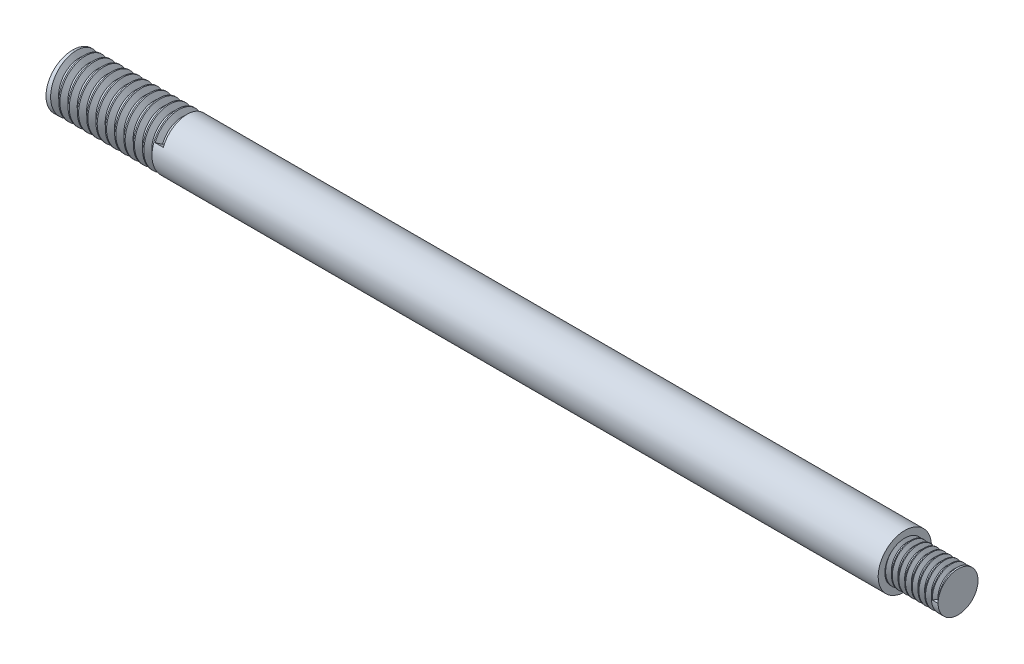
SolidWorks part; units mm, degrees
ref_plane "Front Plane" through (0, 0, 0) normal (0, 0, 1) x (1, 0, 0)
ref_plane "Top Plane" through (0, 0, 0) normal (0, 1, 0) x (1, 0, 0)
ref_plane "Right Plane" through (0, 0, 0) normal (1, 0, 0) x (0, 0, -1)
sketch "Sketch1" plane through (0, 0, 0) normal (0, 0, 1) x (1, 0, 0)
  line L0 (0, 0) -> (0, 2)
  line L1 (0, 2) -> (62.5, 2)
  line L2 (62.5, 2) -> (62.5, 1.5)
  line L3 (62.5, 1.5) -> (66.5, 1.5)
  line L4 (66.5, 1.5) -> (66.5, 0)
  line L5 (66.5, 0) -> (0, 0)
  dimension "D1" = 62.5
  dimension "D2" = 4
  dimension "D3" = 1.5
  dimension "D4" = 2
revolve "Revolve1" add sketch "Sketch1" angle 360 about L5
thread "Thread1" pitch 0.7 method cut profile "Thread Profile1" start angle 0, offset 0, length 8, pitch 0.7, diameter 4
ref_plane "Plane1" through (0, 0, -2) normal (0, -1, 0) x (0, 0, -1)
sketch "Thread Profile1" plane through (0, 0, -2) normal (0, -1, 0) x (0, 0, -1)
  line L0 (0, 0) -> (0, 0.7) construction
  line L11 (0, 0) -> (0, 0.6125)
  line L12 (0, 0.6125) -> (-0.3789, 0.3937)
  line L13 (-0.3789, 0.3937) -> (-0.3789, 0.2187)
  line L15 (-0.3789, 0.2187) -> (0, 0)
  line L17 (-0.3789, 0.3062) -> (0, 0.3062) construction
  point P2 (0, 0)
  dimension "Pitch" = 0.7
  dimension "Profile_Angle" = 60
  dimension "Profile_Land" = 0.175
  dimension "Profile_Height" = 0.3789
thread "Thread2" pitch 0.5 method cut profile "Thread Profile2" start angle 0, offset 0, length 4, pitch 0.5, diameter 3
ref_plane "Plane2" through (66.5, 0, 1.5) normal (0, -1, 0) x (0, 0, 1)
sketch "Thread Profile2" plane through (66.5, 0, 1.5) normal (0, -1, 0) x (0, 0, 1)
  line L0 (0, 0) -> (0, 0.5) construction
  line L11 (0, 0) -> (0, 0.4375)
  line L12 (0, 0.4375) -> (-0.2706, 0.2812)
  line L13 (-0.2706, 0.2812) -> (-0.2706, 0.1562)
  line L15 (-0.2706, 0.1562) -> (0, 0)
  line L17 (-0.2706, 0.2187) -> (0, 0.2187) construction
  point P2 (0, 0)
  dimension "Pitch" = 0.5
  dimension "Profile_Angle" = 60
  dimension "Profile_Land" = 0.125
  dimension "Profile_Height" = 0.2706
